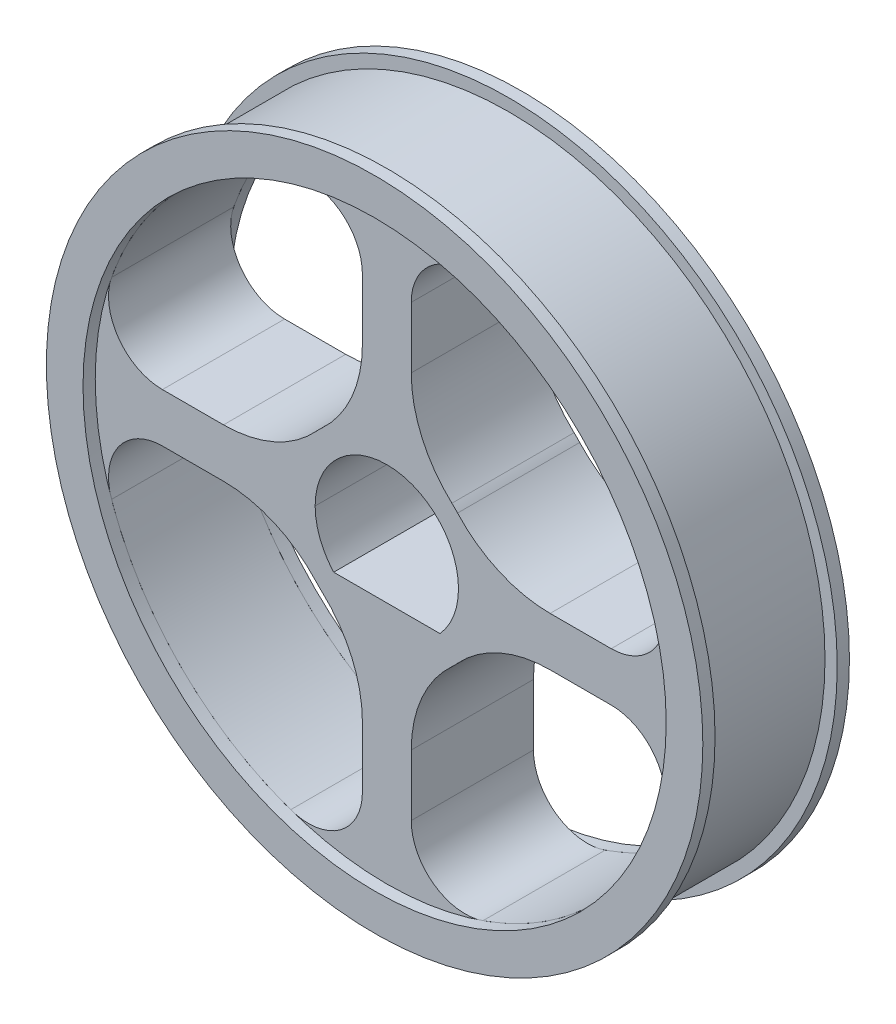
SolidWorks part; units mm, degrees
material "ABS"
ref_plane "Front Plane" through (0, 0, 0) normal (0, 0, 1) x (1, 0, 0)
ref_plane "Top Plane" through (0, 0, 0) normal (0, 1, 0) x (1, 0, 0)
ref_plane "Right Plane" through (0, 0, 0) normal (1, 0, 0) x (0, 0, -1)
sketch "Sketch1" plane through (0, 0, 0) normal (0, 0, 1) x (1, 0, 0)
  line L0 (-14.5852, 8.3594) -> (-14.5852, 12.4234) construction
  line L2 (-14.0772, 11.0264) -> (-14.0772, 9.7564)
  line L3 (-13.4806, 5.3614) -> (-15.6898, 5.3614)
  line L4 (-15.0932, 11.0264) -> (-15.0932, 9.7564)
  line L5 (-9.9202, 6.8694) -> (-11.1902, 6.8694)
  line L6 (-14.5852, 10.3914) -> (-15.0932, 10.3914) construction
  line L7 (-9.9202, 5.8534) -> (-11.1902, 5.8534)
  line L8 (-14.0772, 1.6964) -> (-14.0772, 2.9664)
  line L9 (-15.0932, 1.6964) -> (-15.0932, 2.9664)
  line L10 (-19.2502, 5.8534) -> (-17.9802, 5.8534)
  line L11 (-19.2502, 6.8694) -> (-17.9802, 6.8694)
  circle A1 centre (-14.5852, 6.3614) radius 1.998
  circle A5 centre (-14.5852, 6.3614) radius 6.062
  arc A6 (-13.0952, 6.3614) -> (-16.0752, 6.3614) centre (-14.5852, 6.3614) ccw
  circle A7 centre (-14.5852, 6.3614) radius 6.57
  circle A8 centre (-14.5852, 6.3614) radius 6.824
  arc A9 (-15.0932, 11.0264) -> (-16.5835, 12.0846) centre (-16.214, 11.0264) ccw
  arc A10 (-15.0932, 9.7564) -> (-15.9378, 7.8319) centre (-17.708, 9.7564) cw
  arc A11 (-14.0772, 9.7564) -> (-13.2326, 7.8319) centre (-11.4624, 9.7564) ccw
  arc A12 (-14.0772, 11.0264) -> (-12.5869, 12.0846) centre (-12.9564, 11.0264) cw
  arc A13 (-11.1902, 6.8694) -> (-13.1147, 7.714) centre (-11.1902, 9.4842) cw
  arc A14 (-9.9202, 6.8694) -> (-8.862, 8.3597) centre (-9.9202, 7.9902) ccw
  arc A15 (-9.9202, 5.8534) -> (-8.862, 4.3631) centre (-9.9202, 4.7326) cw
  arc A16 (-11.1902, 5.8534) -> (-13.1147, 5.0088) centre (-11.1902, 3.2386) ccw
  arc A17 (-14.0772, 2.9664) -> (-13.2326, 4.8909) centre (-11.4624, 2.9664) cw
  arc A18 (-14.0772, 1.6964) -> (-12.5869, 0.6382) centre (-12.9564, 1.6964) ccw
  arc A19 (-15.0932, 1.6964) -> (-16.5835, 0.6382) centre (-16.214, 1.6964) cw
  arc A20 (-15.0932, 2.9664) -> (-15.9378, 4.8909) centre (-17.708, 2.9664) ccw
  arc A21 (-17.9802, 5.8534) -> (-16.0557, 5.0088) centre (-17.9802, 3.2386) cw
  arc A22 (-19.2502, 5.8534) -> (-20.3083, 4.3631) centre (-19.2502, 4.7326) ccw
  arc A23 (-19.2502, 6.8694) -> (-20.3083, 8.3597) centre (-19.2502, 7.9902) cw
  arc A24 (-17.9802, 6.8694) -> (-16.0557, 7.714) centre (-17.9802, 9.4842) ccw
  spline S6 degree 3 poles (-16.0752, 6.3614) (-16.0746, 6.3309) (-16.0736, 6.27) (-16.0649, 6.179) (-16.0487, 6.0737) (-16.0209, 5.9549) (-15.9774, 5.8248) (-15.9223, 5.6991) (-15.8557, 5.5793) (-15.779, 5.4654) (-15.7195, 5.3961) (-15.6898, 5.3614) knots 0 0 0 0 0.083398 0.166639 0.250037 0.375031 0.500025 0.625018 0.750012 0.875006 1 1 1 1
  spline S7 degree 3 poles (-13.4806, 5.3614) (-13.4605, 5.3843) (-13.4205, 5.4302) (-13.3658, 5.5035) (-13.3072, 5.5925) (-13.248, 5.6992) (-13.1929, 5.8248) (-13.1494, 5.9549) (-13.1184, 6.0885) (-13.0988, 6.2244) (-13.0964, 6.3157) (-13.0952, 6.3614) knots 0 0 0 0 0.083398 0.166639 0.250037 0.375031 0.500025 0.625018 0.750012 0.875006 1 1 1 1
  point P64 (-14.5852, 6.3614)
  dimension "D1" = 0.508
  dimension "D2" = 0.508
  dimension "D3" = 5.08
  dimension "D4" = 0.254
  dimension "D5" = 0.508
  dimension "D6" = 1.27
  dimension "D7" = 4
extrude "Boss-Extrude1" add sketch "Sketch1" along normal mid plane 2.54 contours A7 A5 | L2 A12 A5 A9 L4 A10 A1 A11 | A16 L7 A15 A5 A14 L5 A13 A1 | A24 L11 A23 A5 A22 L10 A21 A1 | A20 L9 A19 A5 A18 L8 A17 A1 | A1 S7 L3 S6 A6 region at (-14.5852, 10.481, 0) region at (-13.2123, 7.7342, 0) region at (-10.4656, 6.3614, 0) region at (-18.7048, 6.3614, 0) region at (-14.5852, 2.2418, 0) region at (-20.9693, 6.3614, 0)
extrude "Boss-Extrude2" add sketch "Sketch1<5>" along normal blind 0.254 from surface separate body contours A7 A5 | A8 A7 region at (-20.9693, 6.3614, 0) region at (-21.2162, 6.3614, 0) starting at face at (-12.1016, 3.8778, 1.27)
sketch "Sketch1<5>" plane through (0, 0, 0) normal (0, 0, 1) x (1, 0, 0) same geometry as "Sketch1"
mirror "Mirror2" about plane through (0, 0, 0) normal (0, 0, 1) of bodies 105 102
